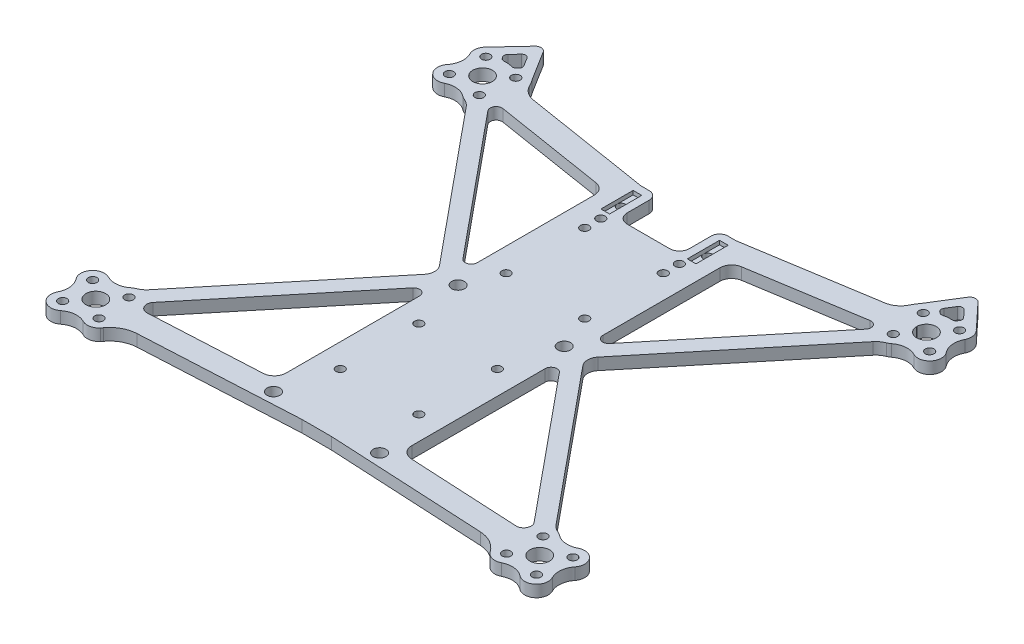
SolidWorks part; units mm, degrees
ref_plane "Front Plane" through (0, 0, 0) normal (0, 0, 1) x (1, 0, 0)
ref_plane "Top Plane" through (0, 0, 0) normal (0, 1, 0) x (1, 0, 0)
ref_plane "Right Plane" through (0, 0, 0) normal (1, 0, 0) x (0, 0, -1)
sketch "Sketch1" plane through (0, 0, 0) normal (0, 1, 0) x (1, 0, 0)
  line L0 (0, 42.225) -> (0, -42.225) construction
  line L1 (16, 42.225) -> (-16, 42.225)
  line L2 (16, 42.225) -> (16, -42.225)
  line L3 (16, -42.225) -> (-16, -42.225)
  line L4 (-16, 42.225) -> (-16, -42.225)
  line L5 (16, 42.225) -> (-16, -42.225) construction
  line L6 (16, -42.225) -> (-16, 42.225) construction
  line L12 (-12.1, 50.425) -> (-12.1, 52.425) construction
  line L17 (-11, 52.425) -> (-11, 42.225) construction
  line L18 (-7.9, 42.225) -> (-14.1, 42.225)
  line L20 (-10, 36) -> (10, 36)
  line L21 (-10, 36) -> (-10, 16)
  line L22 (-10, 16) -> (10, 16)
  line L23 (10, 36) -> (10, 16)
  line L24 (-10, 36) -> (10, 16) construction
  line L25 (-10, 16) -> (10, 36) construction
  line L26 (-14.5, 10.775) -> (14.5, 10.775)
  line L27 (-14.5, 10.775) -> (-14.5, 41.225)
  line L28 (-14.5, 41.225) -> (14.5, 41.225)
  line L29 (14.5, 10.775) -> (14.5, 41.225)
  line L30 (-14.5, 10.775) -> (14.5, 41.225) construction
  line L31 (-14.5, 41.225) -> (14.5, 10.775) construction
  line L32 (-10, -6.225) -> (10, -6.225)
  line L33 (-10, -6.225) -> (-10, -26.225)
  line L34 (-10, -26.225) -> (10, -26.225)
  line L35 (10, -6.225) -> (10, -26.225)
  line L36 (-10, -6.225) -> (10, -26.225) construction
  line L37 (-10, -26.225) -> (10, -6.225) construction
  line L38 (-15.75, -36.225) -> (15.75, -36.225)
  line L39 (-15.75, -36.225) -> (-15.75, 3.775)
  line L40 (-15.75, 3.775) -> (15.75, 3.775)
  line L41 (15.75, -36.225) -> (15.75, 3.775)
  line L42 (-15.75, -36.225) -> (15.75, 3.775) construction
  line L43 (-15.75, 3.775) -> (15.75, -36.225) construction
  line L48 (-7.9, 42.225) -> (-7.9, 52.425)
  line L49 (-7.9, 52.425) -> (-14.1, 52.425)
  line L59 (-14.1, 42.225) -> (-14.1, 52.425)
  line L63 (-12.1, 50.425) -> (-9.9, 50.425)
  line L64 (-12.1, 50.425) -> (-12.1, 42.225)
  line L65 (-12.1, 42.225) -> (-9.9, 42.225)
  line L66 (-9.9, 50.425) -> (-9.9, 42.225)
  line L67 (-12.1, 50.425) -> (-9.9, 42.225) construction
  line L68 (-12.1, 42.225) -> (-9.9, 50.425) construction
  line L69 (-12.1, 50.425) -> (-14.1, 50.425) construction
  line L74 (7.9, 42.225) -> (14.1, 42.225)
  line L75 (14.1, 42.225) -> (14.1, 52.425)
  line L76 (7.9, 52.425) -> (14.1, 52.425)
  line L77 (7.9, 42.225) -> (7.9, 52.425)
  line L78 (12.1, 50.425) -> (9.9, 50.425)
  line L79 (12.1, 50.425) -> (12.1, 42.225)
  line L80 (12.1, 42.225) -> (9.9, 42.225)
  line L81 (9.9, 50.425) -> (9.9, 42.225)
  line L82 (-14.5, 10.775) -> (-14.5, 3.775) construction
  line L83 (-14.5, 7.275) -> (16, 7.275) construction
  line L89 (-13.5, -37.225) -> (-16, -37.225) construction
  line L94 (-14.1, 52.425) -> (-16, 52.425)
  line L95 (-14.1, 52.425) -> (-14.1, 42.225)
  line L96 (-14.1, 42.225) -> (-16, 42.225)
  line L97 (-16, 52.425) -> (-16, 42.225)
  line L98 (14.1, 52.425) -> (16, 52.425)
  line L99 (14.1, 52.425) -> (14.1, 42.225)
  line L100 (14.1, 42.225) -> (16, 42.225)
  line L101 (16, 52.425) -> (16, 42.225)
  circle A3 centre (-10, 36) radius 1.1
  circle A4 centre (10, 36) radius 1.1
  circle A5 centre (10, 16) radius 1.1
  circle A6 centre (-10, 16) radius 1.1
  circle A7 centre (-10, -6.225) radius 1.1
  circle A8 centre (10, -6.225) radius 1.1
  circle A9 centre (10, -26.225) radius 1.1
  circle A10 centre (-10, -26.225) radius 1.1
  circle A37 centre (-13.5, 7.275) radius 2.5
  circle A38 centre (-13.5, 7.275) radius 1.625
  circle A39 centre (13.5, 7.275) radius 1.625
  circle A40 centre (-13.5, -39.725) radius 2.5
  circle A41 centre (-13.5, -39.725) radius 1.625
  circle A42 centre (13.5, -39.725) radius 1.625
  point P0 (0, 0)
  point P8 (0, 0)
  point P16 (0, 26)
  point P26 (0, 26)
  point P31 (0, -16.225)
  point P36 (0, -16.225)
  point P61 (-11, 46.325)
  dimension "D3" = 2
  dimension "D17" = 2.2
  dimension "D22" = 5
  dimension "D23" = 3.25
  dimension "D8" = 32
  dimension "D9" = 22
  dimension "D10" = 20
  dimension "D11" = 29
  dimension "D12" = 30.45
  dimension "D13" = 40
  dimension "D14" = 31.5
  dimension "D15" = 1
  dimension "D16" = 7
  dimension "D18" = 2.2
  dimension "D20" = 8.2
  dimension "D24" = 1
extrude "Base shape" add sketch "Sketch1" along normal blind 2 contours L63 L66 L1 L48 L49 L59 L18 L64 | L81 L78 L79 L1 L75 L76 L77 | L94 L97 L1 L59 | L101 L98 L75 L1 | L1 L4 L3 L2 | A4 | A3 | A7 | A8 | A9 | A10 | A5 | A6 | A39 | A38 | A41 | A42 region at (15.05, 0, -47.325) region at (13.1, 0, -42.3444) region at (-8.9, 0, -42.3444) region at (-15.05, 0, -47.325)
sketch "Sketch2" plane through (0, 0, 0) normal (0, -1, 0) x (1, 0, 0)
  line L0 (-12.1, -42.225) -> (-9.9, -50.425) construction
  line L1 (12.1, -42.225) -> (9.9, -50.425) construction
  line L4 (12.1, -42.225) -> (9.9, -42.225)
  line L5 (12.1, -50.425) -> (12.1, -42.225)
  line L6 (9.9, -50.425) -> (12.1, -50.425)
  line L7 (9.9, -42.225) -> (9.9, -50.425)
  line L8 (12.1, -42.225) -> (9.9, -42.225)
  line L9 (12.1, -50.425) -> (12.1, -42.225)
  line L10 (9.9, -50.425) -> (12.1, -50.425)
  line L11 (9.9, -42.225) -> (9.9, -50.425)
  line L12 (-9.9, -42.225) -> (-12.1, -42.225)
  line L13 (-9.9, -50.425) -> (-9.9, -42.225)
  line L14 (-12.1, -50.425) -> (-9.9, -50.425)
  line L15 (-12.1, -42.225) -> (-12.1, -50.425)
  line L16 (-9.9, -42.225) -> (-12.1, -42.225)
  line L17 (-9.9, -50.425) -> (-9.9, -42.225)
  line L18 (-12.1, -50.425) -> (-9.9, -50.425)
  line L19 (-12.1, -42.225) -> (-12.1, -50.425)
  circle A0 centre (-11, -46.325) radius 1.1
  circle A1 centre (11, -46.325) radius 1.1
  line M9 (9.9, -42.225) -> (12.1, -42.225)
  line M10 (12.1, -42.225) -> (12.1, -50.425)
  line M11 (12.1, -50.425) -> (9.9, -50.425)
  line M12 (9.9, -50.425) -> (9.9, -42.225)
  line M13 (-12.1, -42.225) -> (-9.9, -42.225)
  line M14 (-9.9, -42.225) -> (-9.9, -50.425)
  line M15 (-9.9, -50.425) -> (-12.1, -50.425)
  line M16 (-12.1, -50.425) -> (-12.1, -42.225)
  dimension "D1" = 0
  dimension "D2" = 0
extrude "Camera mount pockets" add sketch "Sketch2" against normal offset from surface (1 mm away) 1 contours A0 L19 M14 M13 | A0 L17 M16 M15 | A1 L9 M12 M11 | A1 L11 M10 M9 region at (11, 0, -43.8523) region at (11, 0, -48.7977) region at (-11, 0, -43.8523) region at (-11, 0, -48.7977) up to face at (11, 2, -46.325)
fillet "Main fillets" radius 2.5 6 edges at (7.9, 1, -42.225) (-7.9, 1, -42.225) (-16, 1, -52.425) (16, 1, -52.425) (-16, 1, 42.225) (16, 1, 42.225)
fillet "Inner camera mount fillets" radius 2.1 2 edges at (-7.9, 1, -52.425) (7.9, 1, -52.425)
sketch "Sketch3" plane through (0, 2, 0) normal (0, 1, 0) x (1, 0, 0)
  line L6 (12.1, 42.225) -> (12.1, 50.425)
  line L7 (9.9, 42.225) -> (12.1, 42.225)
  line L8 (-10, 52.425) -> (-13.5, 52.425)
  line L9 (-16, 49.925) -> (-16, -39.725)
  line L10 (-13.5, -42.225) -> (13.5, -42.225)
  line L11 (16, -39.725) -> (16, 49.925)
  line L12 (13.5, 52.425) -> (10, 52.425)
  line L13 (7.9, 50.325) -> (7.9, 44.725)
  line L14 (5.4, 42.225) -> (-5.4, 42.225)
  line L15 (-7.9, 44.725) -> (-7.9, 50.325)
  line L16 (-10, 52.425) -> (-13.5, 52.425)
  line L17 (-16, 49.925) -> (-16, -39.725)
  line L18 (-13.5, -42.225) -> (13.5, -42.225)
  line L19 (16, -39.725) -> (16, 49.925)
  line L20 (13.5, 52.425) -> (10, 52.425)
  line L21 (7.9, 50.325) -> (7.9, 44.725)
  line L22 (5.4, 42.225) -> (-5.4, 42.225)
  line L23 (-7.9, 44.725) -> (-7.9, 50.325)
  line L24 (9.9, 50.425) -> (9.9, 42.225)
  line L25 (12.1, 50.425) -> (9.9, 50.425)
  line L26 (12.1, 42.225) -> (12.1, 50.425)
  line L27 (9.9, 42.225) -> (12.1, 42.225)
  line L28 (9.9, 50.425) -> (9.9, 42.225)
  line L29 (12.1, 50.425) -> (9.9, 50.425)
  line L30 (-9.9, 42.225) -> (-9.9, 50.425)
  line L31 (-12.1, 42.225) -> (-9.9, 42.225)
  line L32 (-12.1, 50.425) -> (-12.1, 42.225)
  line L33 (-9.9, 50.425) -> (-12.1, 50.425)
  line L34 (-9.9, 42.225) -> (-9.9, 50.425)
  line L35 (-12.1, 42.225) -> (-9.9, 42.225)
  line L36 (-12.1, 50.425) -> (-12.1, 42.225)
  line L37 (-9.9, 50.425) -> (-12.1, 50.425)
  circle A0 centre (13.5, -39.725) radius 1.625 construction
  circle A1 centre (-13.5, -39.725) radius 1.625 construction
  circle A2 centre (-13.5, 7.275) radius 1.625 construction
  circle A3 centre (-10, -6.225) radius 1.1 construction
  circle A4 centre (-10, -26.225) radius 1.1 construction
  circle A5 centre (10, -26.225) radius 1.1 construction
  circle A6 centre (10, -6.225) radius 1.1 construction
  circle A7 centre (13.5, 7.275) radius 1.625 construction
  arc A8 (-13.5, 52.425) -> (-16, 49.925) centre (-13.5, 49.925) ccw
  arc A9 (-16, -39.725) -> (-13.5, -42.225) centre (-13.5, -39.725) ccw
  arc A10 (13.5, -42.225) -> (16, -39.725) centre (13.5, -39.725) ccw
  arc A11 (16, 49.925) -> (13.5, 52.425) centre (13.5, 49.925) ccw
  arc A12 (-7.9, 50.325) -> (-10, 52.425) centre (-10, 50.325) ccw
  arc A13 (5.4, 42.225) -> (7.9, 44.725) centre (5.4, 44.725) ccw
  arc A14 (-7.9, 44.725) -> (-5.4, 42.225) centre (-5.4, 44.725) ccw
  arc A15 (-7.9, 50.325) -> (-10, 52.425) centre (-10, 50.325) ccw
  arc A16 (-13.5, 52.425) -> (-16, 49.925) centre (-13.5, 49.925) ccw
  arc A17 (-16, -39.725) -> (-13.5, -42.225) centre (-13.5, -39.725) ccw
  arc A18 (13.5, -42.225) -> (16, -39.725) centre (13.5, -39.725) ccw
  arc A19 (16, 49.925) -> (13.5, 52.425) centre (13.5, 49.925) ccw
  arc A21 (5.4, 42.225) -> (7.9, 44.725) centre (5.4, 44.725) ccw
  arc A22 (-7.9, 44.725) -> (-5.4, 42.225) centre (-5.4, 44.725) ccw
  circle A24 centre (-10, 16) radius 1.1 construction
  circle A25 centre (-10, 36) radius 1.1 construction
  circle A26 centre (10, 36) radius 1.1 construction
  circle A27 centre (10, 16) radius 1.1 construction
  circle A28 centre (10, 16) radius 1.1
  circle A29 centre (10, 36) radius 1.1
  circle A30 centre (-10, 36) radius 1.1
  circle A31 centre (-10, 16) radius 1.1
  circle A32 centre (13.5, 7.275) radius 1.625
  circle A33 centre (10, -6.225) radius 1.1
  circle A34 centre (10, -26.225) radius 1.1
  circle A35 centre (-10, -26.225) radius 1.1
  circle A36 centre (-10, -6.225) radius 1.1
  circle A37 centre (13.5, -39.725) radius 1.625
  circle A38 centre (-13.5, -39.725) radius 1.625
  circle A39 centre (-13.5, 7.275) radius 1.625
  arc A48 (10, 52.425) -> (7.9, 50.325) centre (10, 50.325) ccw
  arc A49 (10, 52.425) -> (7.9, 50.325) centre (10, 50.325) ccw
  dimension "D1" = 0
  dimension "D2" = 0
  dimension "D3" = 0
extrude "Thicker base" add sketch "Sketch3" along normal blind 1
sketch "Sketch8" plane through (0, 1, 0) normal (0, 1, 0) x (1, 0, 0)
  line L0 (-9.9, 42.225) -> (-9.9, 46.325) construction
  line L1 (-12.1, 46.325) -> (-12.1, 42.225) construction
  line L2 (-12.1, 42.225) -> (-9.9, 42.225) construction
  line L3 (-12.1, 50.425) -> (-12.1, 46.325) construction
  line L4 (-9.9, 46.325) -> (-9.9, 50.425) construction
  line L5 (-9.9, 50.425) -> (-12.1, 50.425) construction
  line L6 (9.9, 50.425) -> (9.9, 46.325) construction
  line L7 (12.1, 46.325) -> (12.1, 50.425) construction
  line L8 (12.1, 50.425) -> (9.9, 50.425) construction
  line L9 (12.1, 42.225) -> (12.1, 46.325) construction
  line L10 (9.9, 46.325) -> (9.9, 42.225) construction
  line L11 (9.9, 42.225) -> (12.1, 42.225) construction
  line L12 (-9.9, 42.225) -> (-9.9, 46.325)
  line L13 (-12.1, 46.325) -> (-12.1, 42.225)
  line L14 (-12.1, 42.225) -> (-9.9, 42.225)
  line L15 (-12.1, 50.425) -> (-12.1, 46.325)
  line L16 (-9.9, 46.325) -> (-9.9, 50.425)
  line L17 (-9.9, 50.425) -> (-12.1, 50.425)
  line L18 (9.9, 50.425) -> (9.9, 46.325)
  line L19 (12.1, 46.325) -> (12.1, 50.425)
  line L20 (12.1, 50.425) -> (9.9, 50.425)
  line L21 (12.1, 42.225) -> (12.1, 46.325)
  line L22 (9.9, 46.325) -> (9.9, 42.225)
  line L23 (9.9, 42.225) -> (12.1, 42.225)
  arc A0 (-12.1, 46.325) -> (-9.9, 46.325) centre (-11, 46.325) ccw construction
  arc A1 (-9.9, 46.325) -> (-12.1, 46.325) centre (-11, 46.325) ccw construction
  arc A2 (12.1, 46.325) -> (9.9, 46.325) centre (11, 46.325) ccw construction
  arc A3 (9.9, 46.325) -> (12.1, 46.325) centre (11, 46.325) ccw construction
  arc A4 (-12.1, 46.325) -> (-9.9, 46.325) centre (-11, 46.325) ccw
  arc A5 (-9.9, 46.325) -> (-12.1, 46.325) centre (-11, 46.325) ccw
  arc A6 (12.1, 46.325) -> (9.9, 46.325) centre (11, 46.325) ccw
  arc A7 (9.9, 46.325) -> (12.1, 46.325) centre (11, 46.325) ccw
  line M1 (12.1, 42.225) -> (12.1, 46.325)
  arc M2 (12.1, 46.325) -> (9.9, 46.325) centre (11, 46.325) cw
  line M3 (9.9, 46.325) -> (9.9, 42.225)
  line M4 (9.9, 42.225) -> (12.1, 42.225)
extrude "Boss-Extrude1" add sketch "Sketch8" along normal offset from surface (1 mm away) 1 contours A6 L19 L20 L18 | M4 M1 M2 M3 | A5 L16 L17 L15 | A4 L13 L14 L12 region at (-11, 1, -43.8523) region at (-11, 1, -48.7977) region at (11, 1, -48.7977) region at (11, 1, -43.8523) up to face at (-13.5, 3, 41.35)
sketch "Sketch4" plane through (0, 0, 0) normal (0, -1, 0) x (1, 0, 0)
  line L0 (0, 13.9568) -> (0, -8.6953) construction
  line L1 (-13.1, -38.5) -> (-6.9, -38.5)
  line L2 (-14.1, -39.5) -> (-14.1, -40.7)
  line L3 (-13.1, -41.7) -> (-6.9, -41.7)
  line L4 (-5.9, -39.5) -> (-5.9, -40.7)
  line L5 (-10, -38.5) -> (-10, -41.7) construction
  line L7 (13.1, -38.5) -> (6.9, -38.5)
  line L8 (14.1, -39.5) -> (14.1, -40.7)
  line L9 (13.1, -41.7) -> (6.9, -41.7)
  line L10 (5.9, -39.5) -> (5.9, -40.7)
  line L12 (-14.1, -40.1) -> (-5.9, -40.1) construction
  circle A0 centre (-10, -36) radius 2
  arc A9 (14.1, -40.7) -> (13.1, -41.7) centre (13.1, -40.7) cw
  arc A10 (13.1, -38.5) -> (14.1, -39.5) centre (13.1, -39.5) cw
  arc A11 (6.9, -41.7) -> (5.9, -40.7) centre (6.9, -40.7) cw
  arc A12 (6.9, -38.5) -> (5.9, -39.5) centre (6.9, -39.5) ccw
  arc A13 (-6.9, -41.7) -> (-5.9, -40.7) centre (-6.9, -40.7) ccw
  arc A14 (-6.9, -38.5) -> (-5.9, -39.5) centre (-6.9, -39.5) cw
  arc A15 (-14.1, -40.7) -> (-13.1, -41.7) centre (-13.1, -40.7) ccw
  arc A16 (-13.1, -38.5) -> (-14.1, -39.5) centre (-13.1, -39.5) ccw
  point P9 (-10, -38)
  point P19 (14.1, -41.7)
  point P24 (14.1, -38.5)
  point P27 (5.9, -41.7)
  point P30 (5.9, -38.5)
  point P33 (-5.9, -41.7)
  point P36 (-5.9, -38.5)
  point P39 (-14.1, -41.7)
  point P42 (-14.1, -38.5)
  dimension "D5" = 4
  dimension "D6" = 1
  dimension "D1" = 8.2
  dimension "D2" = 3.2
  dimension "D3" = 10
  dimension "D4" = 0.5
extrude "Battery holder pockets" cut sketch "Sketch4" against normal blind 1 contours L4 L1 L2 L3 | L7 L10 L9 L8 region at (-10, 0, -40.1) region at (10, 0, -40.1)
sketch "Sketch5" plane through (0, 1, 0) normal (0, -1, 0) x (1, 0, 0)
  line L0 (-10, -38.5) -> (-10, -41.7) construction
  line L2 (-13.1, -41.7) -> (-6.9, -41.7) construction
  line L3 (0, 5.9884) -> (0, -5.6723) construction
  line L4 (-13.1, -38.5) -> (-6.9, -38.5) construction
  circle A0 centre (-10, -40.1) radius 1.1
  circle A1 centre (10, -40.1) radius 1.1
  point P2 (-10, -38.5)
  dimension "D1" = 2.2
extrude "Battery holder holes" cut sketch "Sketch5" against normal up to next
sketch "Sketch6" [suppressed] plane through (0, 0, 0) normal (0, -1, 0) x (1, 0, 0)
  line L0 (0, -5.1) -> (0, 9.653) construction
  line L8 (-13.5, -7.275) -> (13.5, -7.275) construction
  line L10 (-16, -25.775) -> (16, -25.775) construction
  line L11 (-16, -49.925) -> (-16, 39.725) construction
  line L12 (16, -49.925) -> (16, 39.725) construction
  line L13 (17.5, -34.275) -> (19, -34.275)
  line L14 (16, -37.275) -> (19, -37.275)
  line L15 (16, -37.275) -> (16, -14.275)
  line L16 (16, -14.275) -> (19, -14.275)
  line L17 (19, -37.275) -> (19, -14.275)
  line L18 (16, -37.275) -> (19, -14.275) construction
  line L19 (16, -14.275) -> (19, -37.275) construction
  line L20 (16, -35.775) -> (17.5, -35.775)
  line L21 (16, -35.775) -> (16, -15.775)
  line L22 (16, -15.775) -> (17.5, -15.775)
  line L23 (17.5, -35.775) -> (17.5, -15.775)
  line L24 (16, -35.775) -> (17.5, -15.775) construction
  line L25 (16, -15.775) -> (17.5, -35.775) construction
  line L26 (17.5, -17.275) -> (19, -17.275)
  line L27 (-17.5, -34.275) -> (-19, -34.275)
  line L28 (-17.5, -17.275) -> (-19, -17.275)
  line L29 (-16, -35.775) -> (-16, -15.775)
  line L30 (-16, -35.775) -> (-17.5, -35.775)
  line L31 (-17.5, -35.775) -> (-17.5, -15.775)
  line L32 (-16, -15.775) -> (-17.5, -15.775)
  line L33 (-16, -37.275) -> (-16, -14.275)
  line L34 (-16, -37.275) -> (-19, -37.275)
  line L35 (-19, -37.275) -> (-19, -14.275)
  line L36 (-16, -14.275) -> (-19, -14.275)
  line L37 (16, 22.725) -> (19, 22.725)
  line L38 (16, 22.725) -> (16, -0.275)
  line L39 (16, -0.275) -> (19, -0.275)
  line L40 (19, 22.725) -> (19, -0.275)
  line L41 (16, 21.225) -> (17.5, 21.225)
  line L42 (16, 21.225) -> (16, 1.225)
  line L43 (16, 1.225) -> (17.5, 1.225)
  line L44 (17.5, 21.225) -> (17.5, 1.225)
  line L45 (17.5, 2.725) -> (19, 2.725)
  line L46 (17.5, 19.725) -> (19, 19.725)
  line L47 (-17.5, 19.725) -> (-19, 19.725)
  line L48 (-17.5, 2.725) -> (-19, 2.725)
  line L49 (-16, 21.225) -> (-16, 1.225)
  line L50 (-16, 21.225) -> (-17.5, 21.225)
  line L51 (-17.5, 21.225) -> (-17.5, 1.225)
  line L52 (-16, 1.225) -> (-17.5, 1.225)
  line L53 (-16, 22.725) -> (-16, -0.275)
  line L54 (-16, 22.725) -> (-19, 22.725)
  line L55 (-19, 22.725) -> (-19, -0.275)
  line L56 (-16, -0.275) -> (-19, -0.275)
  point P19 (17.5, -25.775)
  point P25 (16.75, -25.775)
  line M18 (16, -49.925) -> (16, 39.725)
  line M22 (-16, 39.725) -> (-16, -49.925)
  dimension "D1" = 14
  dimension "D4" = 23
  dimension "D5" = 3
  dimension "D6" = 1.5
  dimension "D7" = 20
  dimension "D8" = 1.5
extrude "Strap holders" [suppressed] add sketch "Sketch6" against normal up to surface (2 mm away) contours L23 L20 L14 L17 L13 M18 | L23 L26 L17 L16 L22 M18 | L45 L44 L43 L39 L40 M18 | L44 L46 L40 L37 L38 L41 | L54 L55 L47 L51 L50 M22 | L56 L52 L51 L48 L55 M22 | L36 L35 L28 L31 L32 M22 | L35 L34 L30 L31 L27 M22 up to face at (11, 2, -48.65)
fillet "Strap holder fillets" [suppressed] radius 0.75
sketch "Sketch7" plane through (0, 3, 0) normal (0, 1, 0) x (1, 0, 0)
  line L0 (-56.5, 56.5) -> (-16, 50.0116) construction
  line L1 (56.5, -56.5) -> (-56.5, -56.5)
  line L2 (56.5, -56.5) -> (56.5, 56.5)
  line L3 (56.5, 56.5) -> (-56.5, 56.5)
  line L4 (-56.5, -56.5) -> (-56.5, 56.5)
  line L5 (56.5, -56.5) -> (-56.5, 56.5) construction
  line L6 (56.5, 56.5) -> (-56.5, -56.5) construction
  line L7 (-16, 49.925) -> (-16, -39.725) construction
  line L8 (-56.9746, 53.5378) -> (-16.4746, 47.0493)
  line L9 (-47.647, 58.1199) -> (-12.1, 52.425)
  line L10 (-56.0254, 59.4622) -> (-15.5254, 52.9738) construction
  line L11 (-13.5, 7.275) -> (13.5, 7.275) construction
  line L12 (-63.45, 50.7819) -> (-49.55, 62.2181) construction
  line L13 (-56.5, 56.5) -> (-16, 7.275) construction
  line L14 (-58.0444, 55.2293) -> (-17.5444, 6.0043)
  line L15 (-54.9556, 57.7707) -> (-14.4556, 8.5457)
  line L16 (-17.5444, 6.0043) -> (-16, 4.1271)
  line L17 (-56.5, 56.5) -> (-60.3121, 61.1333) construction
  line L18 (-56.5, 65.5) -> (-56.5, 47.5) construction
  line L19 (-60.3121, 61.1333) -> (-51.8667, 60.3121) construction
  line L20 (-56.0894, 60.7227) -> (-55.3151, 68.6852) construction
  line L21 (-56.4116, 69.7087) -> (-62.3842, 63.31)
  line L22 (-54.0419, 69.4782) -> (-49.414, 62.0488)
  line L23 (-55.4603, 67.1922) -> (-58.7341, 63.6848)
  line L24 (-55.4603, 67.1922) -> (-52.9235, 63.1198)
  line L25 (-58.0444, -40.6793) -> (-17.5444, 8.5457)
  line L26 (-54.9556, -43.2207) -> (-14.4556, 6.0043)
  line L27 (-56.5, -41.95) -> (-13.5, -39.725) construction
  line L28 (-47.871, -44.5075) -> (-3.7595, -42.225)
  line L29 (-56.655, -38.954) -> (-16, -36.8503)
  line L30 (-56.345, -44.946) -> (-14.5762, -42.7847) construction
  line L31 (-56.5, -41.95) -> (-14.7312, -39.7887) construction
  line L32 (-13.5, -42.225) -> (13.5, -42.225) construction
  line L33 (-56.655, -38.954) -> (-14.8862, -36.7927) construction
  line L34 (-16.4746, 47.0493) -> (-16, 46.9733)
  line L35 (-12.1, 50.425) -> (-12.1, 52.425) construction
  line L36 (-10, 52.425) -> (-13.5, 52.425) construction
  circle A0 centre (-56.5, 56.5) radius 38.1
  circle A1 centre (-56.5, 56.5) radius 9
  circle A2 centre (-56.5, 56.5) radius 6
  circle A3 centre (-51.8667, 60.3121) radius 1.1
  circle A4 centre (-61.1333, 52.6879) radius 1.1
  circle A5 centre (-60.3121, 61.1333) radius 1.1
  circle A6 centre (-52.6879, 51.8667) radius 1.1
  circle A7 centre (-60.3121, 61.1333) radius 3
  circle A8 centre (-51.8667, 60.3121) radius 3
  circle A9 centre (-61.1333, 52.6879) radius 3
  circle A10 centre (-52.6879, 51.8667) radius 3
  circle A12 centre (-56.5, 56.5) radius 2.5
  circle A13 centre (-55.3151, 68.6852) radius 1.5
  circle A14 centre (-67.313, 57.5515) radius 4.864
  circle A15 centre (-57.5515, 45.687) radius 4.864
  circle A16 centre (-43.9819, 62.4587) radius 4.864
  circle A17 centre (-55.5501, 44.5421) radius 4.864
  circle A18 centre (-46.9606, 50.4143) radius 1.5
  circle A20 centre (-56.5, -41.95) radius 6
  circle A21 centre (-52.6879, -37.3167) radius 1.1
  circle A22 centre (-61.1333, -38.1379) radius 1.1
  circle A23 centre (-60.3121, -46.5833) radius 1.1
  circle A24 centre (-51.8667, -45.7621) radius 1.1
  circle A25 centre (-51.8667, -45.7621) radius 3
  circle A26 centre (-52.6879, -37.3167) radius 3
  circle A27 centre (-56.5, -41.95) radius 2.5
  circle A28 centre (-60.3121, -46.5833) radius 3
  circle A29 centre (-67.313, -43.0015) radius 4.864
  circle A30 centre (-61.1333, -38.1379) radius 3
  circle A31 centre (-57.5515, -31.137) radius 4.864
  circle A32 centre (-55.5501, -29.9921) radius 4.864
  circle A34 centre (-56.5, -41.95) radius 9
  circle A35 centre (-55.4485, -52.763) radius 4.864
  circle A38 centre (-43.36, -51.5674) radius 7.2836
  circle A39 centre (-47.0369, -36.5665) radius 1.8873
  point P0 (0, 0)
  point P36 (-52.6879, 51.8667)
  point P54 (-55.4603, 67.1922)
  arc M21 (-7.9, 50.325) -> (-10, 52.425) centre (-10, 50.325) ccw
  line M22 (-10, 52.425) -> (-13.5, 52.425)
  arc M23 (-13.5, 52.425) -> (-16, 49.925) centre (-13.5, 49.925) ccw
  line M24 (-16, 49.925) -> (-16, -39.725)
  arc M25 (-16, -39.725) -> (-13.5, -42.225) centre (-13.5, -39.725) ccw
  line M26 (-13.5, -42.225) -> (13.5, -42.225)
  dimension "D3" = 76.2
  dimension "D4" = 12
  dimension "D5" = 3
  dimension "D10" = 2.2
  dimension "D11" = 5
  dimension "D12" = 3
  dimension "D16" = 3
  dimension "D1" = 113
  dimension "D13" = 8
  dimension "D6" = 3
  dimension "D7" = 3
  dimension "D8" = 2
  dimension "D9" = 2
  dimension "D14" = 3
  dimension "D15" = 3
extrude "Arms" add sketch "Sketch7" against normal up to surface (3 mm away) contours A0 L8 L34 L9 M24 M23 M22 M21 | A1 L8 A0 L9 L3 | A10 L8 A1 L3 A2 | A16 L3 L9 | A8 A2 L3 A1 | A2 A8 A3 | A2 A8 A3 | A12 L3 A2 A8 A7 A9 L4 L14 | A12 L15 A10 A2 L3 | A12 L4 L8 A10 L15 | A12 L14 L8 L4 | A10 L8 L4 L14 | A10 L14 L4 A2 | L8 L14 L4 | A14 A9 A2 | A14 A2 A7 | A15 A2 A9 | A15 A10 A2 L4 | A10 L15 A1 L8 | A10 A1 L15 | A17 A1 L14 A10 | A10 L14 A1 | A17 L14 A1 | A1 L14 A0 L15 | A8 A1 L24 | A13 L24 A1 L22 | A13 | A13 L21 A1 L23 | A7 L23 A1 | A0 L14 L16 L15 M24 | L25 A34 L26 L16 L14 | L29 A34 L28 M26 M25 M24 | A39 L26 A34 | A39 A34 L29 | A34 L25 A26 | A34 A32 A26 L25 | A32 A34 L25 | A26 A31 L4 A20 | L4 A31 A20 | L25 A26 A20 L4 | A20 A30 A28 L4 A27 L25 | A20 A31 A30 | A20 A30 A29 | A20 A29 A28 | A35 L4 A20 A28 | A35 A25 A20 | L26 A27 L4 A20 A25 A26 | A35 A20 L4 | L4 A27 L26 A26 L29 | L29 A26 L25 L4 | L25 L29 L4 | L25 A27 L4 L29 | A38 L28 A34 | A34 L29 A26 A20 A25 | A34 L26 A26 L29 | A34 A26 L26 | A15 L4 A2 | A18 L8 A1 L15 | A1 L3 L9 | A7 | A5 | A9 | A4 | A10 | A6 | A26 | A21 | A30 | A22 | A28 | A23 | A25 | A24 region at (-47.184, 3, 45.066) region at (-31.3338, 3, 40.711) region at (-32.8289, 3, -52.5874) region at (-44.211, 3, -57.0386) region at (-17.1717, 3, -50.3538) region at (-48.9969, 3, 41.7471) region at (-49.1236, 3, -54.6581) region at (-48.8324, 3, -58.0351) region at (-47.1282, 3, -58.5028) region at (-24.1765, 3, -17.1136) region at (-41.5668, 3, -38.3497) region at (-57.4052, 3, 48.163) region at (-54.4445, 3, 47.8724) region at (-51.8807, 3, -55.6768) region at (-52.205, 3, -56.6697) region at (-49.2822, 3, -51.8002) region at (-48.4949, 3, -51.2849) region at (-52.3363, 3, -48.2332) region at (-34.0657, 3, 14.6748) region at (-56.355, 3, 47.9664) region at (-62.4224, 3, 44.0055) region at (-57.252, 3, 47.2609) region at (-55.1154, 3, 47.6835) region at (-48.0098, 3, 38.2823) region at (-49.1686, 3, 37.7777) region at (-54.4837, 3, -54.6883) region at (-53.0659, 3, -59.3254) region at (-50.9193, 3, -61.0916) region at (-49.7951, 3, -50.7418) region at (-52.9788, 3, -65.9755) region at (-52.3363, 3, 33.6832) region at (-52.9015, 3, -48.7171) region at (-52.1414, 3, -48.8113) region at (-49.026, 3, 36.4293) region at (-55.3151, 3, -68.6852) region at (-52.4447, 3, -63.9477) region at (-52.1414, 3, 34.2613) region at (-52.9015, 3, 34.1671) region at (-58.5555, 3, 36.0276) region at (-58.5555, 3, -50.5776) region at (-62.7075, 3, 41.0741) region at (-49.7951, 3, 36.1918) region at (-56.6984, 3, -53.811) region at (-55.8748, 3, -53.0321) region at (-58.1296, 3, -66.4764) region at (-55.5948, 3, 35.737) region at (-56.645, 3, 35.9336) region at (-56.645, 3, -50.4836) region at (-55.5948, 3, -50.287) region at (-62.7075, 3, -55.6241) region at (-56.701, 3, 39.2669) region at (-54.4356, 3, 40.1886) region at (-56.5346, 3, -53.4308) region at (-56.0913, 3, -51.6584) region at (-59.0444, 3, -64.5895) region at (-56.0913, 3, 37.1084) region at (-62.4224, 3, -58.5555) region at (-56.5412, 3, 38.9002) region at (-55.8564, 3, 38.5438) up to face at (-13.5, 0, 41.35)
fillet "Motor protector fillets" radius 1 5 edges at (-52.9235, 1.5, -63.1198) (-54.2913, 1.5, -62.0787) (-57.5925, 1.5, -62.3997) (-58.7341, 1.5, -63.6848) (-55.4603, 1.5, -67.1922)
mirror "Arms mirror" about plane through (0, 0, 0) normal (1, 0, 0) of "Arms", "Motor protector fillets"
fillet "Arm fillets outer" radius 3 6 edges at (-16, 1.5, 36.8503) (-16, 1.5, -46.9733) (-18.5899, 1.5, -7.275) (16, 1.5, 36.8503) (18.5899, 1.5, -7.275) (16, 1.5, -46.9733)
fillet "Arm fillets inner" radius 1.5 4 edges at (-16, 1.5, -10.4229) (-16, 1.5, -4.1271) (16, 1.5, -4.1271) (16, 1.5, -10.4229)
